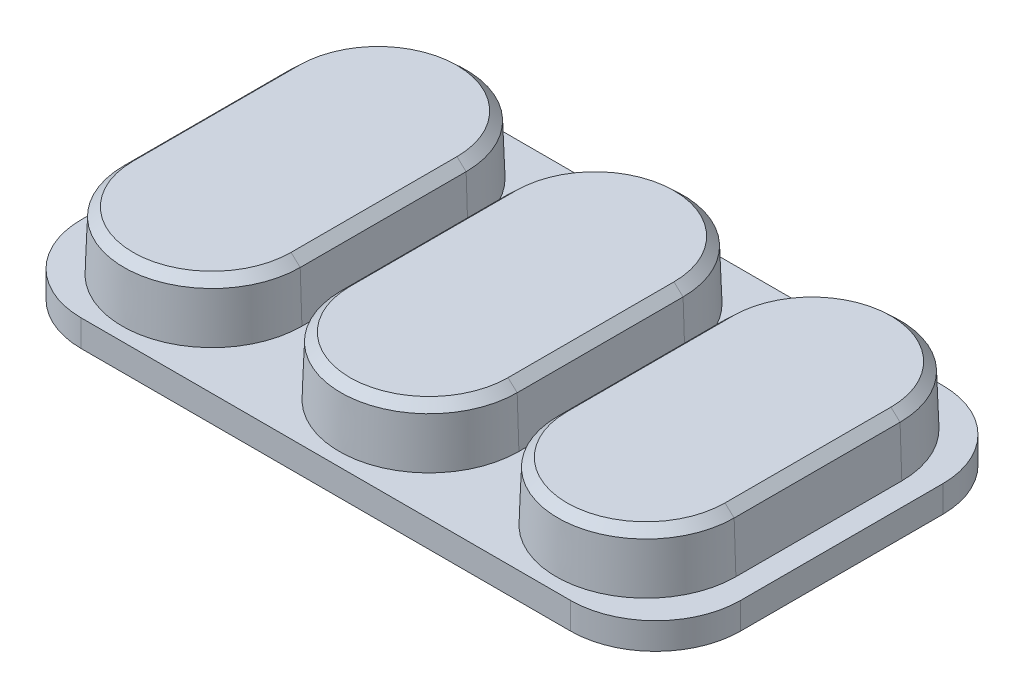
SolidWorks part; units mm, degrees
ref_plane "Front Plane" through (0, 0, 0) normal (0, 0, 1) x (1, 0, 0)
ref_plane "Top Plane" through (0, 0, 0) normal (0, 1, 0) x (1, 0, 0)
ref_plane "Right Plane" through (0, 0, 0) normal (1, 0, 0) x (0, 0, -1)
sketch "Sketch1" plane through (0, 0, 0) normal (0, 1, 0) x (1, 0, 0)
  line L0 (-31, -17.5) -> (31, 17.5) construction
  line L1 (-23, 17.5) -> (23, 17.5)
  line L2 (-31, 9.5) -> (-31, -9.5)
  line L3 (-23, -17.5) -> (23, -17.5)
  line L4 (31, 9.5) -> (31, -9.5)
  arc A0 (23, 17.5) -> (31, 9.5) centre (23, 9.5) cw
  arc A1 (23, -17.5) -> (31, -9.5) centre (23, -9.5) ccw
  arc A2 (-31, -9.5) -> (-23, -17.5) centre (-23, -9.5) ccw
  arc A3 (-23, 17.5) -> (-31, 9.5) centre (-23, 9.5) ccw
  point P4 (0, 0)
  point P16 (-31, 17.5)
  dimension "D3" = 8
  dimension "D1" = 62
  dimension "D2" = 35
extrude "Boss-Extrude1" add sketch "Sketch1" along normal blind 2.5
sketch "Sketch2" plane through (0, 2.5, 0) normal (0, 1, 0) x (1, 0, 0)
  line L0 (0, 17.5) -> (0, -17.5) construction
  line L1 (23, 17.5) -> (-23, 17.5) construction
  line L2 (-23, -17.5) -> (23, -17.5) construction
  line L3 (-20.4, -7.8) -> (-20.4, 7.8) construction
  line L4 (-28.85, -7.8) -> (-28.85, 7.8)
  line L5 (-11.95, -7.8) -> (-11.95, 7.8)
  line L6 (-31, 0) -> (31, 0) construction
  line L7 (-31, 9.5) -> (-31, -9.5) construction
  line L8 (31, -9.5) -> (31, 9.5) construction
  line L9 (0, -7.8) -> (0, 7.8) construction
  line L10 (-8.45, -7.8) -> (-8.45, 7.8)
  line L11 (8.45, -7.8) -> (8.45, 7.8)
  line L12 (20.4, -7.8) -> (20.4, 7.8) construction
  line L13 (11.95, -7.8) -> (11.95, 7.8)
  line L14 (28.85, -7.8) -> (28.85, 7.8)
  line L15 (-20.4, -7.8) -> (0, -7.8) construction
  arc A0 (-28.85, -7.8) -> (-11.95, -7.8) centre (-20.4, -7.8) ccw
  arc A1 (-11.95, 7.8) -> (-28.85, 7.8) centre (-20.4, 7.8) ccw
  arc A2 (-8.45, -7.8) -> (8.45, -7.8) centre (0, -7.8) ccw
  arc A3 (8.45, 7.8) -> (-8.45, 7.8) centre (0, 7.8) ccw
  arc A4 (11.95, -7.8) -> (28.85, -7.8) centre (20.4, -7.8) ccw
  arc A5 (28.85, 7.8) -> (11.95, 7.8) centre (20.4, 7.8) ccw
  point P8 (-20.4, 0)
  point P21 (0, 0)
  point P28 (-20.4, 16.25)
  point P29 (-20.4, -16.25)
  point P30 (20.4, 0)
  point P33 (0, 0)
  point P39 (20, 0)
  point P40 (20, -7.55)
  point P41 (28.2, -7.55)
  point P42 (-20, -7.55)
  dimension "D1" = 16.9
  dimension "D2" = 32.5
  dimension "D4" = 20.4
  dimension "D5" = 3.5
  dimension "D3" = 3
extrude "Boss-Extrude2" add sketch "Sketch2" along normal blind 5.5
chamfer "Chamfer2" distance 5.5 angle 2 12 edges at (-28.85, 8, 0) (-20.4, 8, -16.25) (-11.95, 8, 0) (-20.4, 8, 16.25) (-8.45, 8, 0) (0, 8, -16.25) (8.45, 8, 0) (0, 8, 16.25) (11.95, 8, 0) (20.4, 8, -16.25) (28.85, 8, 0) (20.4, 8, 16.25) first distance on face at (-28.85, 5.25, 0) first distance on face at (-20.4, 5.25, -12.025) first distance on face at (-11.95, 5.25, 0) first distance on face at (-20.4, 5.25, 12.025) first distance on face at (-8.45, 5.25, 0) first distance on face at (0, 5.25, -12.025) first distance on face at (8.45, 5.25, 0) first distance on face at (0, 5.25, 12.025) first distance on face at (11.95, 5.25, 0) first distance on face at (20.4, 5.25, -12.025) first distance on face at (28.85, 5.25, 0) first distance on face at (20.4, 5.25, 12.025)
chamfer "Chamfer3" distance 0.8 angle 45 12 edges at (-12.1421, 8, 0) (-20.4, 8, 16.0579) (-28.6579, 8, 0) (-20.4, 8, -16.0579) (8.2579, 8, 0) (0, 8, 16.0579) (-8.2579, 8, 0) (0, 8, -16.0579) (28.6579, 8, 0) (20.4, 8, 16.0579) (12.1421, 8, 0) (20.4, 8, -16.0579) first distance on face at (-12.046, 5.25, 0) first distance on face at (-20.4, 5.25, 11.977) first distance on face at (-28.754, 5.25, 0) first distance on face at (-20.4, 5.25, -11.977) first distance on face at (8.354, 5.25, 0) first distance on face at (0, 5.25, 11.977) first distance on face at (-8.354, 5.25, 0) first distance on face at (0, 5.25, -11.977) first distance on face at (28.754, 5.25, 0) first distance on face at (20.4, 5.25, 11.977) first distance on face at (12.046, 5.25, 0) first distance on face at (20.4, 5.25, -11.977)
